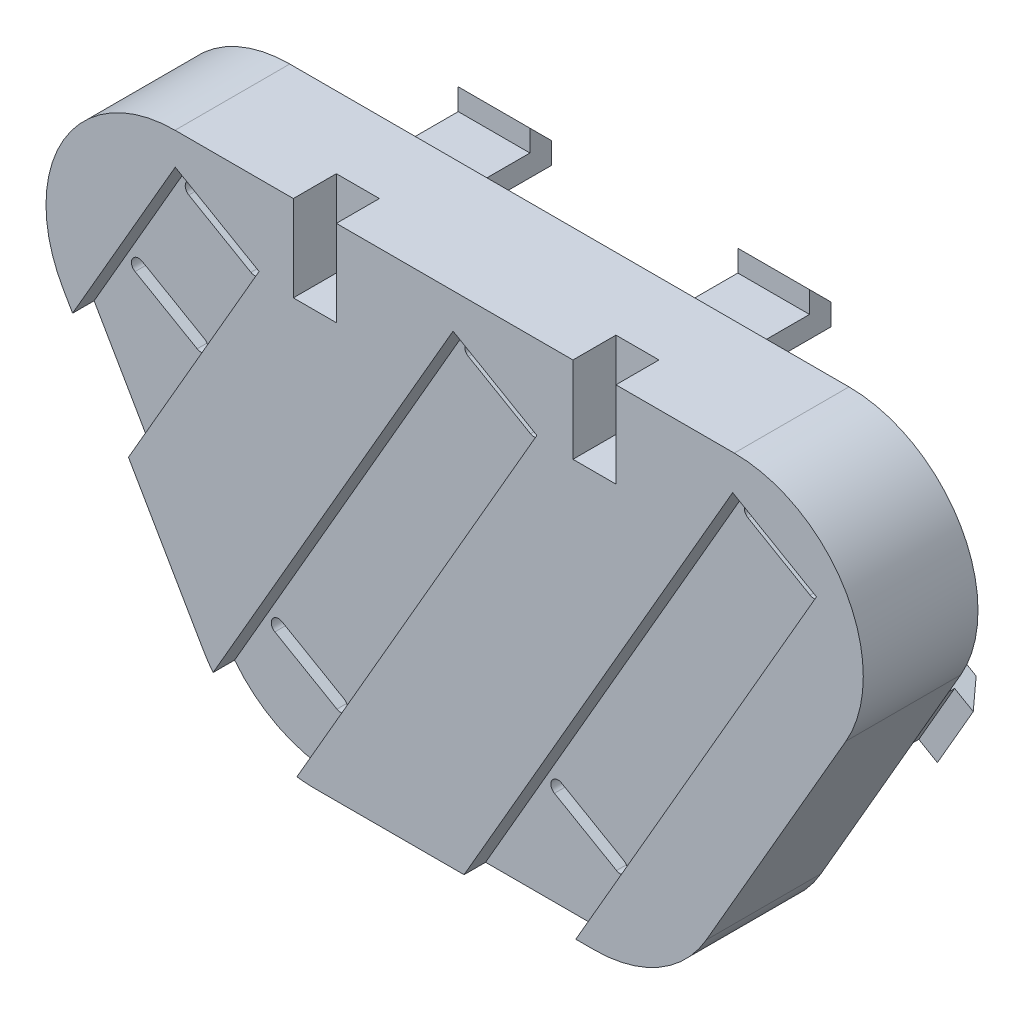
SolidWorks part; units mm, degrees
ref_plane "Front Plane" through (0, 0, 0) normal (0, 0, 1) x (1, 0, 0)
ref_plane "Top Plane" through (0, 0, 0) normal (0, 1, 0) x (1, 0, 0)
ref_plane "Right Plane" through (0, 0, 0) normal (1, 0, 0) x (0, 0, -1)
sketch "Sketch1" plane through (0, 0, 0) normal (0, 0, 1) x (1, 0, 0)
  line L0 (0, 0) -> (-19.5, 0) construction
  line L1 (-9.75, -16.8875) -> (-29.25, -16.8875) construction
  line L2 (0, 0) -> (-9.75, -16.8875) construction
  line L3 (-9.75, -16.8875) -> (-19.5, 0) construction
  line L4 (-19.5, 0) -> (-29.25, -16.8875) construction
  line L5 (-29.25, -16.8875) -> (-39, 0) construction
  line L6 (-39, 0) -> (-19.5, 0) construction
  line L7 (8.9827, 0.5584) -> (-5.4199, -24.3875) construction
  line L8 (-5.4199, -24.3875) -> (-33.5801, -24.3875) construction
  line L9 (-33.5801, -24.3875) -> (-47.9827, 0.5584) construction
  line L10 (-43.9749, 7.5) -> (4.9749, 7.5) construction
  line L11 (7.7942, -4.5) -> (-1.9558, -21.3875)
  line L12 (-9.75, -25.8875) -> (-29.25, -25.8875)
  line L13 (-37.0442, -21.3875) -> (-46.7942, -4.5)
  line L14 (-39, 9) -> (0, 9)
  line L15 (1.7814, -11.9145) -> (3.0804, -12.6645) construction
  line L16 (-19.5, -24.3875) -> (-19.5, -25.8875) construction
  line L17 (-40.7814, -11.9145) -> (-42.0804, -12.6645) construction
  line L18 (-19.5, 7.5) -> (-19.5, 9) construction
  circle A0 centre (-29.25, -16.8875) radius 7.5
  circle A1 centre (-19.5, 0) radius 7.5
  circle A2 centre (0, 0) radius 7.5
  circle A3 centre (0, 0) radius 7.5
  circle A4 centre (-9.75, -16.8875) radius 7.5
  circle A5 centre (-39, 0) radius 7.5
  arc A6 (7.7942, -4.5) -> (0, 9) centre (0, 0) ccw
  arc A7 (-39, 9) -> (-46.7942, -4.5) centre (-39, 0) ccw
  arc A8 (-1.9558, -21.3875) -> (-9.75, -25.8875) centre (-9.75, -16.8875) cw
  arc A9 (-29.25, -25.8875) -> (-37.0442, -21.3875) centre (-29.25, -16.8875) cw
  point P28 (1.7814, -11.9145)
  point P30 (-19.5, -24.3875)
  point P32 (-40.7814, -11.9145)
  point P35 (-19.5, 9)
  dimension "D2" = 15
  dimension "D3" = 19.5
  dimension "D4" = 1.5
  dimension "D5" = 1.5
  dimension "D1" = 0.25
extrude "Boss-Extrude1" add sketch "Sketch1" along normal blind 5
sketch "Sketch2" plane through (0, 0, 5) normal (0, 0, 1) x (1, 0, 0)
  line L0 (-1.9558, -21.3875) -> (7.7942, -4.5) construction
  line L1 (0, 9) -> (-39, 9) construction
  line L2 (-46.7942, -4.5) -> (-37.0442, -21.3875) construction
  line L3 (-29.25, -25.8875) -> (-9.75, -25.8875) construction
  line L4 (-1.9558, -21.3875) -> (7.7942, -4.5)
  line L5 (0, 9) -> (-39, 9)
  line L6 (-46.7942, -4.5) -> (-37.0442, -21.3875)
  line L7 (-29.25, -25.8875) -> (-9.75, -25.8875)
  line L8 (4.0401, 1.9976) -> (-0.2901, 4.4976) construction
  line L9 (3.7901, 1.5646) -> (-0.5401, 4.0646)
  line L10 (4.2901, 2.4306) -> (-0.0401, 4.9306)
  line L11 (-9.4599, -21.3851) -> (-13.7901, -18.8851) construction
  line L12 (-9.7099, -21.8181) -> (-14.0401, -19.3181)
  line L13 (-9.2099, -20.9521) -> (-13.5401, -18.4521)
  line L14 (1.875, 3.2476) -> (-11.625, -20.1351) construction
  line L15 (-31.125, -20.1351) -> (-29.25, -16.8875) construction
  line L16 (0, 0) -> (1.875, 3.2476) construction
  line L17 (1.875, 3.2476) -> (3.75, 6.4952) construction
  line L18 (-11.625, -20.1351) -> (-13.5, -23.3827) construction
  line L19 (-11.625, -20.1351) -> (-9.75, -16.8875) construction
  line L20 (-17.625, 3.2476) -> (-15.75, 6.4952) construction
  line L21 (-17.625, 3.2476) -> (-31.125, -20.1351) construction
  line L22 (-19.5, 0) -> (-17.625, 3.2476) construction
  line L23 (-31.125, -20.1351) -> (-33, -23.3827) construction
  line L24 (-15.4599, 1.9976) -> (-19.7901, 4.4976) construction
  line L25 (-15.7099, 1.5646) -> (-20.0401, 4.0646)
  line L26 (-15.2099, 2.4306) -> (-19.5401, 4.9306)
  line L27 (-28.9599, -21.3851) -> (-33.2901, -18.8851) construction
  line L28 (-29.2099, -21.8181) -> (-33.5401, -19.3181)
  line L29 (-28.7099, -20.9521) -> (-33.0401, -18.4521)
  line L30 (-34.9599, 1.9976) -> (-39.2901, 4.4976) construction
  line L31 (-35.2099, 1.5646) -> (-39.5401, 4.0646)
  line L32 (-34.7099, 2.4306) -> (-39.0401, 4.9306)
  line L33 (-38.7099, -4.4976) -> (-43.0401, -1.9976) construction
  line L34 (-38.9599, -4.9306) -> (-43.2901, -2.4306)
  line L35 (-38.4599, -4.0646) -> (-42.7901, -1.5646)
  line L36 (-37.125, 3.2476) -> (-40.875, -3.2476) construction
  line L37 (-37.125, 3.2476) -> (-35.25, 6.4952) construction
  line L38 (-40.875, -3.2476) -> (-42.75, -6.4952) construction
  line L39 (-37.125, 3.2476) -> (-39, 0) construction
  arc A0 (-9.75, -25.8875) -> (-1.9558, -21.3875) centre (-9.75, -16.8875) ccw construction
  arc A1 (7.7942, -4.5) -> (0, 9) centre (0, 0) ccw construction
  arc A2 (-39, 9) -> (-46.7942, -4.5) centre (-39, 0) ccw construction
  arc A3 (-37.0442, -21.3875) -> (-29.25, -25.8875) centre (-29.25, -16.8875) ccw construction
  arc A4 (-9.75, -25.8875) -> (-1.9558, -21.3875) centre (-9.75, -16.8875) ccw
  arc A5 (7.7942, -4.5) -> (0, 9) centre (0, 0) ccw
  arc A6 (-39, 9) -> (-46.7942, -4.5) centre (-39, 0) ccw
  arc A7 (-37.0442, -21.3875) -> (-29.25, -25.8875) centre (-29.25, -16.8875) ccw
  circle A8 centre (-39, 0) radius 7.5 construction
  circle A9 centre (-29.25, -16.8875) radius 7.5 construction
  circle A10 centre (-19.5, 0) radius 7.5 construction
  circle A11 centre (-9.75, -16.8875) radius 7.5 construction
  circle A12 centre (0, 0) radius 7.5 construction
  circle A13 centre (-39, 0) radius 7.5
  circle A14 centre (-29.25, -16.8875) radius 7.5
  circle A15 centre (-19.5, 0) radius 7.5
  circle A16 centre (-9.75, -16.8875) radius 7.5
  circle A17 centre (0, 0) radius 7.5
  arc A18 (3.7901, 1.5646) -> (4.2901, 2.4306) centre (4.0401, 1.9976) ccw
  arc A19 (-0.0401, 4.9306) -> (-0.5401, 4.0646) centre (-0.2901, 4.4976) ccw
  arc A20 (-9.7099, -21.8181) -> (-9.2099, -20.9521) centre (-9.4599, -21.3851) ccw
  arc A21 (-13.5401, -18.4521) -> (-14.0401, -19.3181) centre (-13.7901, -18.8851) ccw
  arc A22 (-15.7099, 1.5646) -> (-15.2099, 2.4306) centre (-15.4599, 1.9976) ccw
  arc A23 (-19.5401, 4.9306) -> (-20.0401, 4.0646) centre (-19.7901, 4.4976) ccw
  arc A24 (-29.2099, -21.8181) -> (-28.7099, -20.9521) centre (-28.9599, -21.3851) ccw
  arc A25 (-33.0401, -18.4521) -> (-33.5401, -19.3181) centre (-33.2901, -18.8851) ccw
  arc A26 (-35.2099, 1.5646) -> (-34.7099, 2.4306) centre (-34.9599, 1.9976) ccw
  arc A27 (-39.0401, 4.9306) -> (-39.5401, 4.0646) centre (-39.2901, 4.4976) ccw
  arc A28 (-38.9599, -4.9306) -> (-38.4599, -4.0646) centre (-38.7099, -4.4976) ccw
  arc A29 (-42.7901, -1.5646) -> (-43.2901, -2.4306) centre (-43.0401, -1.9976) ccw
  point P8 (-37.125, 3.2476)
  point P25 (1.875, 3.2476)
  point P32 (-11.625, -20.1351)
  point P45 (-17.625, 3.2476)
  point P52 (-31.125, -20.1351)
  point P64 (-40.875, -3.2476)
  circle M1 centre (-9.75, -16.8875) radius 7.5
  circle M2 centre (0, 0) radius 7.5
  arc M3 (7.7942, -4.5) -> (0, 9) centre (0, 0) ccw
  line M4 (0, 9) -> (-39, 9)
  arc M5 (-39, 9) -> (-46.7942, -4.5) centre (-39, 0) ccw
  line M6 (-46.7942, -4.5) -> (-37.0442, -21.3875)
  arc M7 (-37.0442, -21.3875) -> (-29.25, -25.8875) centre (-29.25, -16.8875) ccw
  line M8 (-29.25, -25.8875) -> (-9.75, -25.8875)
  arc M9 (-9.75, -25.8875) -> (-1.9558, -21.3875) centre (-9.75, -16.8875) ccw
  line M10 (-1.9558, -21.3875) -> (7.7942, -4.5)
  circle M11 centre (-19.5, 0) radius 7.5
  circle M12 centre (-29.25, -16.8875) radius 7.5
  circle M13 centre (-39, 0) radius 7.5
  dimension "D1" = 1
  dimension "D2" = 5
extrude "Boss-Extrude2" add sketch "Sketch2" along normal blind 1.5 contours A21 L13 A20 L12 M1 | M10 M3 M4 M5 M6 M7 M8 M9 M2 M11 M13 M12 M1 | A19 L10 A18 L9 M2 | A23 L26 A22 L25 M11 | A25 L29 A24 L28 M12 | A29 L35 A28 L34 A27 L32 A26 L31 M13 region at (-5.5841, -24.103, 5) region at (-39, 0, 5) region at (-29.1865, -16.7776, 5) region at (-19.5635, -0.1099, 5) region at (-9.6865, -16.7776, 5) region at (-0.0635, -0.1099, 5)
sketch "Sketch3" plane through (0, 0, 6.5) normal (0, 0, 1) x (1, 0, 0)
  line L0 (-46.7942, -4.5) -> (-37.0442, -21.3875) construction
  line L1 (-29.25, -25.8875) -> (-9.75, -25.8875) construction
  line L2 (-1.9558, -21.3875) -> (7.7942, -4.5) construction
  line L3 (0, 9) -> (-39, 9) construction
  line L4 (-46.7942, -4.5) -> (-37.0442, -21.3875)
  line L5 (-29.25, -25.8875) -> (-9.75, -25.8875)
  line L6 (-1.9558, -21.3875) -> (7.7942, -4.5)
  line L7 (0, 9) -> (-39, 9)
  line L8 (5.7353, 3.1839) -> (-9.6397, -23.4464)
  line L9 (5.7353, 3.1839) -> (-0.1103, 6.5589)
  line L10 (-9.6397, -23.4464) -> (-15.4853, -20.0714)
  line L11 (-0.1103, 6.5589) -> (-15.4853, -20.0714)
  line L12 (5.7353, 3.1839) -> (-15.4853, -20.0714) construction
  line L13 (-9.6397, -23.4464) -> (-0.1103, 6.5589) construction
  line L14 (-11.625, -20.1351) -> (-13.5, -23.3827) construction
  line L15 (-11.625, -20.1351) -> (-13.5, -23.3827) construction
  line L16 (-11.875, -20.5681) -> (-12.5625, -21.7589) construction
  line L17 (-9.7099, -21.8181) -> (-14.0401, -19.3181) construction
  line L18 (-14.2231, -18.6351) -> (-14.5478, -18.4476) construction
  line L19 (1.875, 3.2476) -> (-11.625, -20.1351) construction
  line L20 (1.875, 3.2476) -> (-11.625, -20.1351) construction
  line L21 (-31.125, -20.1351) -> (-33, -23.3827) construction
  line L22 (-17.625, 3.2476) -> (-31.125, -20.1351) construction
  line L23 (-31.125, -20.1351) -> (-33, -23.3827) construction
  line L24 (-17.625, 3.2476) -> (-31.125, -20.1351) construction
  line L25 (-13.7647, 3.1839) -> (-29.1397, -23.4464)
  line L26 (-13.7647, 3.1839) -> (-19.6103, 6.5589)
  line L27 (-29.1397, -23.4464) -> (-34.9853, -20.0714)
  line L28 (-19.6103, 6.5589) -> (-34.9853, -20.0714)
  line L29 (-13.7647, 3.1839) -> (-34.9853, -20.0714) construction
  line L30 (-29.1397, -23.4464) -> (-19.6103, 6.5589) construction
  line L31 (-32.8571, -19.1351) -> (-34.0478, -18.4476) construction
  line L32 (-31.375, -20.5681) -> (-32.0625, -21.7589) construction
  line L33 (-29.2099, -21.8181) -> (-33.5401, -19.3181) construction
  line L34 (-33.1397, 3.4004) -> (-42.2476, -12.375)
  line L35 (-33.1397, 3.4004) -> (-38.9853, 6.7754)
  line L36 (-9.6397, -23.4464) -> (-15.4853, -20.0714)
  line L37 (-38.9853, 6.7754) -> (-46.1447, -5.625)
  line L38 (-33.1397, 3.4004) -> (-45.4579, -6.8146) construction
  line L39 (-42.2476, -12.375) -> (-38.9853, 6.7754) construction
  line L40 (-37.125, 3.2476) -> (-40.875, -3.2476) construction
  line L41 (-36.875, 3.6806) -> (-36.0625, 5.0879) construction
  line L42 (-34.7099, 2.4306) -> (-39.0401, 4.9306) construction
  line L43 (-36.0625, 5.0879) -> (-35.25, 6.4952) construction
  line L44 (-9.6397, -23.4464) -> (-11.049, -25.8875)
  line L45 (-15.4853, -20.0714) -> (-18.8433, -25.8875)
  line L47 (-29.1397, -23.4464) -> (-34.9853, -20.0714)
  line L48 (-29.1397, -23.4464) -> (-30.4988, -25.8004)
  line L49 (-34.9853, -20.0714) -> (-36.3444, -22.4254)
  arc A0 (-37.0442, -21.3875) -> (-29.25, -25.8875) centre (-29.25, -16.8875) ccw construction
  arc A1 (-9.75, -25.8875) -> (-1.9558, -21.3875) centre (-9.75, -16.8875) ccw construction
  arc A2 (7.7942, -4.5) -> (0, 9) centre (0, 0) ccw construction
  arc A3 (-39, 9) -> (-46.7942, -4.5) centre (-39, 0) ccw construction
  arc A4 (-37.0442, -21.3875) -> (-29.25, -25.8875) centre (-29.25, -16.8875) ccw
  arc A5 (-9.75, -25.8875) -> (-1.9558, -21.3875) centre (-9.75, -16.8875) ccw
  arc A6 (7.7942, -4.5) -> (0, 9) centre (0, 0) ccw
  arc A7 (-39, 9) -> (-46.7942, -4.5) centre (-39, 0) ccw
  arc A8 (-13.5401, -18.4521) -> (-14.0401, -19.3181) centre (-13.7901, -18.8851) ccw construction
  arc A9 (-33.0401, -18.4521) -> (-33.5401, -19.3181) centre (-33.2901, -18.8851) ccw construction
  point P13 (-4.875, -8.4437)
  point P30 (-12.5625, -21.7589)
  point P33 (-4.875, -8.4437)
  point P35 (-24.375, -8.4437)
  point P49 (-24.375, -8.4437)
  point P50 (-40.6165, -2.7998)
  line M15 (-1.9558, -21.3875) -> (7.7942, -4.5)
  arc M16 (7.7942, -4.5) -> (0, 9) centre (0, 0) ccw
  line M17 (0, 9) -> (-39, 9)
  arc M18 (-39, 9) -> (-46.7942, -4.5) centre (-39, 0) ccw
  line M19 (-46.7942, -4.5) -> (-37.0442, -21.3875)
  arc M20 (-37.0442, -21.3875) -> (-29.25, -25.8875) centre (-29.25, -16.8875) ccw
  line M21 (-29.25, -25.8875) -> (-9.75, -25.8875)
  arc M22 (-9.75, -25.8875) -> (-1.9558, -21.3875) centre (-9.75, -16.8875) ccw
extrude "Boss-Extrude3" add sketch "Sketch3" along normal blind 1.5 contours L37 L35 L34 L4 L28 L26 L25 L27 L11 L9 L8 L10 M20 M21 M22 M15 M16 M17 M18 M19 region at (-46.2155, 4.1659, 6.5)
sketch "Sketch4" plane through (0, 0, 0) normal (0, 0, -1) x (-1, 0, 0)
  line L0 (29.25, -25.8875) -> (9.75, -25.8875) construction
  line L1 (22, -25.8875) -> (17, -25.8875)
  line L2 (22, -25.8875) -> (22, -22.8875)
  line L3 (22, -22.8875) -> (17, -22.8875)
  line L4 (17, -25.8875) -> (17, -22.8875)
  line L5 (22, -25.8875) -> (17, -22.8875) construction
  line L6 (22, -22.8875) -> (17, -25.8875) construction
  line L7 (29.25, -25.8875) -> (9.75, -25.8875)
  line L8 (0, 9) -> (39, 9) construction
  line L9 (46.7942, -4.5) -> (37.0442, -21.3875) construction
  line L10 (1.9558, -21.3875) -> (-7.7942, -4.5) construction
  line L11 (0, 9) -> (39, 9)
  line L12 (46.7942, -4.5) -> (37.0442, -21.3875)
  line L13 (1.9558, -21.3875) -> (-7.7942, -4.5)
  line L14 (40.5712, -9.2787) -> (43.1692, -10.7787)
  line L15 (40.5712, -9.2787) -> (38.0712, -13.6088)
  line L16 (43.1692, -10.7787) -> (40.6692, -15.1088)
  line L17 (38.0712, -13.6088) -> (40.6692, -15.1088)
  line L18 (40.5712, -9.2787) -> (40.6692, -15.1088) construction
  line L19 (43.1692, -10.7787) -> (38.0712, -13.6088) construction
  line L20 (-1.5712, -9.2787) -> (-4.1692, -10.7787)
  line L21 (-1.5712, -9.2787) -> (0.9288, -13.6088)
  line L22 (-4.1692, -10.7787) -> (-1.6692, -15.1088)
  line L23 (0.9288, -13.6088) -> (-1.6692, -15.1088)
  line L24 (-1.5712, -9.2787) -> (-1.6692, -15.1088) construction
  line L25 (-4.1692, -10.7787) -> (0.9288, -13.6088) construction
  line L26 (41.9192, -12.9437) -> (3.9115, 9) construction
  line L27 (12.25, 6) -> (7.25, 6)
  line L28 (12.25, 6) -> (12.25, 9)
  line L29 (12.25, 9) -> (7.25, 9)
  line L30 (7.25, 6) -> (7.25, 9)
  line L31 (12.25, 6) -> (7.25, 9) construction
  line L32 (12.25, 9) -> (7.25, 6) construction
  line L33 (31.75, 6) -> (26.75, 6)
  line L34 (31.75, 6) -> (31.75, 9)
  line L35 (31.75, 9) -> (26.75, 9)
  line L36 (26.75, 6) -> (26.75, 9)
  line L37 (31.75, 6) -> (26.75, 9) construction
  line L38 (31.75, 9) -> (26.75, 6) construction
  line L39 (-2.9192, -12.9437) -> (35.0885, 9) construction
  point P0 (19.5, -24.3875)
  point P5 (9.75, 7.5)
  point P8 (19.5, -25.8875)
  point P15 (40.6202, -12.1937)
  point P16 (-1.6202, -12.1937)
  point P29 (29.25, 7.5)
  line M35 (9.75, -25.8875) -> (29.25, -25.8875)
  dimension "D1" = 5
  dimension "D2" = 3
extrude "Boss-Extrude4" add sketch "Sketch4" along normal blind 6 contours L15 L17 L12 L14 | L4 L2 L3 M35 | L23 L21 L20 L13 | L30 L27 L28 L11 | L36 L33 L34 L11 region at (-19.5, -24.3875, 0) region at (-29.25, 7.5, 0) region at (-9.75, 7.5, 0) region at (-40.6202, -12.1937, 0) region at (1.6202, -12.1937, 0)
sketch "Sketch5" plane through (-6.125, 10.6088, 0) normal (-0.5, 0.866, 0) x (0.866, 0.5, 0)
  line L0 (-42.775, 6) -> (-39.775, 6) construction
  line L1 (-42.775, 0) -> (-41.275, 0)
  line L2 (-42.775, 0) -> (-42.775, 4.5)
  line L3 (-42.775, 4.5) -> (-41.275, 4.5)
  line L4 (-41.275, 0) -> (-41.275, 4.5)
  line L5 (-42.775, 4.5) -> (-41.275, 6)
  point P9 (-41.275, 6)
  line M2 (-42.775, 0) -> (-39.775, 0)
  line M4 (-39.775, 6) -> (-42.775, 6)
  line M5 (-42.775, 6) -> (-42.775, 0)
  dimension "D1" = 4.5
extrude "Cut-Extrude1" cut sketch "Sketch5" against normal up to next contours L4 L3 M2 M5 | L5 M5 M4 region at (-42.5197, -10.4037, -2.25) region at (-42.7362, -10.5287, -5.5)
sketch "Sketch7" plane through (-31.75, 0, 0) normal (-1, 0, 0) x (0, 0, 1)
  line L0 (-6, 6) -> (-6, 9) construction
  line L1 (0, 9) -> (-4.5, 9)
  line L2 (0, 9) -> (0, 7.5)
  line L3 (0, 7.5) -> (-4.5, 7.5)
  line L4 (-4.5, 9) -> (-4.5, 7.5)
  line L5 (-4.5, 9) -> (-6, 7.5)
  point P9 (-6, 7.5)
  line M3 (0, 6) -> (0, 9)
  line M4 (0, 9) -> (-6, 9)
  line M5 (-6, 9) -> (-6, 6)
  dimension "D1" = 4.5
extrude "Cut-Extrude2" cut sketch "Sketch7" against normal up to next contours L4 L3 M4 M3 | L5 M4 M5 region at (-31.75, 8.25, -2.25) region at (-31.75, 8.5, -5.5)
ref_axis "Axis1" through (-19.5, -25.8875, -6) along (0, 1, 0)
ref_plane "Plane1" through (-19.5, 0, 0) normal (1, 0, 0) x (0, 1, 0)
mirror "Mirror1" about plane through (-19.5, 0, 0) normal (1, 0, 0) of "Cut-Extrude2", "Cut-Extrude1"
sketch "Sketch8" plane through (-22, 0, 0) normal (-1, 0, 0) x (0, 0, 1)
  line L0 (-4.5, -25.8875) -> (-6, -24.3875)
  line L1 (0, -25.8875) -> (-4.5, -25.8875)
  line L2 (0, -25.8875) -> (0, -24.3875)
  line L3 (0, -24.3875) -> (-4.5, -24.3875)
  line L4 (-4.5, -25.8875) -> (-4.5, -24.3875)
  line L5 (0, -25.8875) -> (0, -22.8875) construction
  line L6 (-6, -25.8875) -> (-6, -22.8875) construction
  line M2 (0, -25.8875) -> (0, -22.8875)
  line M4 (-6, -22.8875) -> (-6, -25.8875)
  line M5 (-6, -25.8875) -> (0, -25.8875)
  dimension "D1" = 4.5
extrude "Cut-Extrude3" cut sketch "Sketch8" against normal up to next contours L0 M5 M4 | L4 L3 M5 M2 region at (-22, -25.3875, -5.5) region at (-22, -25.1375, -2.25)
sketch "Sketch9" plane through (0, 0, 8) normal (0, 0, 1) x (1, 0, 0)
  line L0 (-39, 9) -> (-19.5, 9)
  line L1 (0, 9) -> (-39, 9) construction
  line L2 (-19.5, 9) -> (0, 9) construction
  line L3 (-29.25, 9) -> (-29.25, 3) construction
  line L4 (-27.75, 3) -> (-30.75, 3)
  line L5 (-27.75, 3) -> (-27.75, 9)
  line L6 (-27.75, 9) -> (-30.75, 9)
  line L7 (-30.75, 3) -> (-30.75, 9)
  line L8 (-27.75, 3) -> (-30.75, 9) construction
  line L9 (-27.75, 9) -> (-30.75, 3) construction
  line L10 (-8.25, 3) -> (-11.25, 3)
  line L11 (-8.25, 3) -> (-8.25, 9)
  line L12 (-8.25, 9) -> (-11.25, 9)
  line L13 (-11.25, 3) -> (-11.25, 9)
  line L14 (-8.25, 3) -> (-11.25, 9) construction
  line L15 (-8.25, 9) -> (-11.25, 3) construction
  line L16 (-9.75, 9) -> (-9.75, 3) construction
  point P5 (-29.25, 6)
  point P12 (-9.75, 6)
  dimension "D1" = 3
  dimension "D2" = 6
extrude "Cut-Extrude4" cut sketch "Sketch9" against normal blind 3 contours L10 L13 L12 L11 | L4 L7 L6 L5
equation "\"D3@Sketch1\"=\"D2@Sketch1\"+4.5"
equation "\"D1@Sketch2\"=.65+.35"
